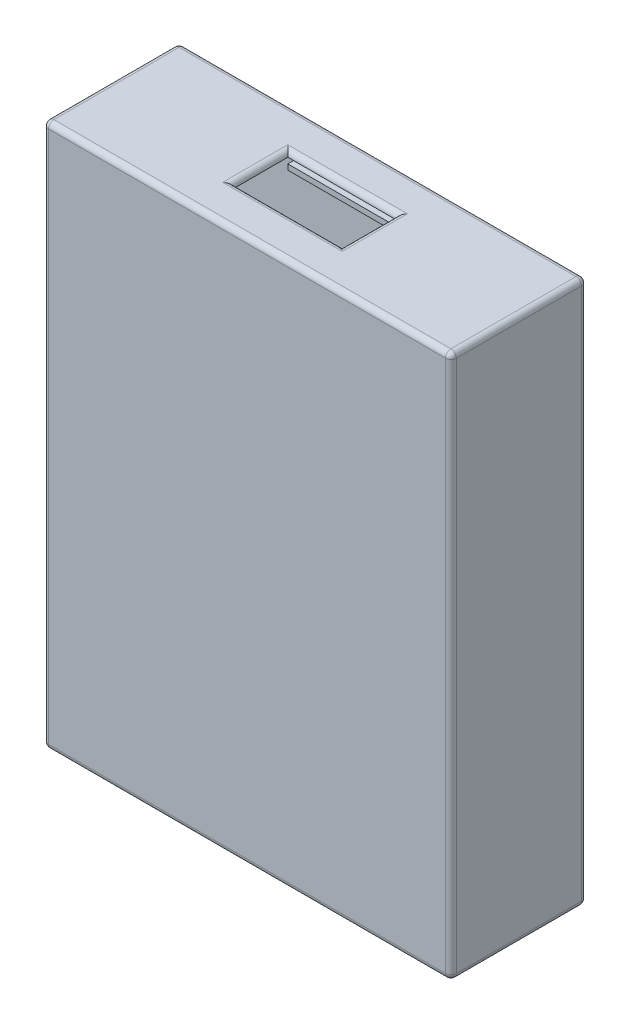
SolidWorks part; units mm, degrees
ref_plane "Front Plane" through (0, 0, 0) normal (0, 0, 1) x (1, 0, 0)
ref_plane "Top Plane" through (0, 0, 0) normal (0, 1, 0) x (1, 0, 0)
ref_plane "Right Plane" through (0, 0, 0) normal (1, 0, 0) x (0, 0, -1)
sketch "Sketch1" plane through (0, 0, 0) normal (0, 1, 0) x (1, 0, 0)
  line L1 (-75, 25) -> (75, 25)
  line L2 (-75, 25) -> (-75, -25)
  line L3 (-75, -25) -> (75, -25)
  line L4 (75, 25) -> (75, -25)
  line L5 (-75, 25) -> (75, -25) construction
  line L6 (-75, -25) -> (75, 25) construction
  point P0 (0, 0)
  dimension "D1" = 150
  dimension "D2" = 50
extrude "Boss-Extrude1" add sketch "Sketch1" along normal blind 30
sketch "Sketch2" plane through (0, 30, 0) normal (0, 1, 0) x (1, 0, 0)
  line L11 (-75, -25) -> (75, -25)
  line L12 (-75, -25) -> (-75, 25)
  line L13 (-75, 25) -> (75, 25)
  line L14 (-73, -23) -> (73, -23)
  line L15 (73, -23) -> (73, 23)
  line L16 (73, 23) -> (-73, 23)
  line L17 (-73, 23) -> (-73, -23)
  line L18 (-73, -23) -> (73, -23)
  line L19 (73, -23) -> (73, 23)
  line L20 (73, 23) -> (-73, 23)
  line L21 (-73, 23) -> (-73, -23)
  line L22 (75, -25) -> (75, 25)
  line L23 (-75, -25) -> (75, 25) construction
  line L24 (-75, 25) -> (75, -25) construction
  point P0 (0, 0)
  dimension "D1" = 2
extrude "Boss-Extrude2" add sketch "Sketch2" along normal blind 168
sketch "Sketch3" plane through (0, 198, 0) normal (0, 1, 0) x (1, 0, 0)
  line L1 (-75, -25) -> (75, -25)
  line L2 (-75, -25) -> (-75, 25)
  line L3 (-75, 25) -> (75, 25)
  line L4 (75, -25) -> (75, 25)
  line L5 (-75, -25) -> (75, 25) construction
  line L6 (-75, 25) -> (75, -25) construction
  point P0 (0, 0)
extrude "Boss-Extrude3" add sketch "Sketch3" along normal blind 2
sketch "Sketch4" plane through (0, 0, -25) normal (0, 0, -1) x (-1, 0, 0)
  line L0 (-73, 30) -> (0, 17.1281)
  line L1 (0, 17.1281) -> (73, 30)
  line L2 (-73, 30) -> (73, 30) construction
  line L3 (-73, 30) -> (73, 30)
  dimension "D1" = 10
  dimension "D2" = 10
extrude "Cut-Extrude1" cut sketch "Sketch4" against normal blind 65
sketch "Sketch6" plane through (0, 30, 0) normal (0, -1, 0) x (1, 0, 0)
  line L1 (-73, 25) -> (73, 25)
  line L2 (-73, 25) -> (-73, 23)
  line L3 (-73, 23) -> (73, 23)
  line L4 (73, 25) -> (73, 23)
extrude "Boss-Extrude13" add sketch "Sketch6" along normal blind 22
sketch "Sketch7" plane through (0, 30, 0) normal (0, -1, 0) x (1, 0, 0)
  line L1 (-73, -23) -> (73, -23)
  line L2 (-73, -23) -> (-73, -25)
  line L3 (-73, -25) -> (73, -25)
  line L4 (73, -23) -> (73, -25)
extrude "Boss-Extrude14" add sketch "Sketch7" along normal blind 22
sketch "Sketch8" plane through (0, 0, -25) normal (0, 0, -1) x (-1, 0, 0)
  circle A0 centre (0, 17.1281) radius 7.5
  dimension "D1" = 15
extrude "Cut-Extrude2" cut sketch "Sketch8" against normal blind 48
sketch "Sketch9" plane through (0, 200, 0) normal (0, 1, 0) x (1, 0, 0)
  line L1 (-20, -10) -> (20, -10)
  line L2 (-20, -10) -> (-20, 10)
  line L3 (-20, 10) -> (20, 10)
  line L4 (20, -10) -> (20, 10)
  line L5 (-20, -10) -> (20, 10) construction
  line L6 (-20, 10) -> (20, -10) construction
  point P0 (0, 0)
  dimension "D1" = 40
  dimension "D2" = 20
extrude "Cut-Extrude3" cut sketch "Sketch9" against normal blind 48
sketch "Sketch10" plane through (0, 0, -25) normal (0, 0, -1) x (-1, 0, 0)
  line L0 (75, 200) -> (-75, 0) construction
  line L1 (-75, 0) -> (-75, 200) construction
  line L2 (-75, 200) -> (75, 0) construction
  line L3 (0, 100) -> (0, 200) construction
  line L4 (-75, 200) -> (75, 200) construction
  line L5 (15.4707, 160) -> (15.4707, 118)
  line L6 (-13.5293, 160) -> (13.4707, 160)
  line L7 (-13.5293, 160) -> (-13.5293, 120)
  line L8 (-13.5293, 120) -> (13.4707, 120)
  line L9 (13.4707, 160) -> (13.4707, 120)
  line L10 (-15.5293, 118) -> (15.4707, 118)
  line L11 (-15.5293, 160) -> (-15.5293, 118)
  line L12 (-13.5293, 160) -> (-15.5293, 160)
  line L13 (13.4707, 160) -> (15.4707, 160)
  line L14 (-15.5293, 160) -> (-13.5293, 160)
  line L15 (13.4707, 160) -> (15.4707, 160)
  line L16 (-13.5293, 120) -> (13.4707, 120)
  circle A0 centre (0, 150) radius 4
  dimension "D1" = 27
  dimension "D2" = 40
  dimension "D3" = 10
  dimension "D4" = 2
extrude "Boss-Extrude15" add sketch "Sketch10" against normal blind 10 contours L13 L9 L8 L7 L12 L11 L10 L5 region at (-14.9487, 139, -25)
extrude "Cut-Extrude4" cut sketch "Sketch10<3>" against normal blind 5 contours A0 region at (0, 150, -25)
sketch "Sketch10<3>" plane through (0, 0, -25) normal (0, 0, -1) x (-1, 0, 0) same geometry as "Sketch10"
sketch "Sketch11" plane through (0, 0, -15) normal (0, 0, 1) x (1, 0, 0)
  line L0 (15.5293, 160) -> (15.5293, 118) construction
  line L1 (-15.4707, 160) -> (15.5293, 160)
  line L2 (-15.4707, 160) -> (-15.4707, 118)
  line L3 (-15.4707, 118) -> (15.5293, 118)
  line L4 (15.5293, 160) -> (15.5293, 118)
  line L5 (15.5293, 118) -> (-15.4707, 118) construction
extrude "Boss-Extrude16" add sketch "Sketch11" along normal blind 2
sketch "Sketch12" plane through (0, 160, 0) normal (0, 1, 0) x (1, 0, 0)
  line L0 (-15.4707, 13) -> (-15.4707, 23) construction
  line L2 (15.5293, 13) -> (-15.4707, 13) construction
  line L3 (-15.4707, 23) -> (-13.4707, 23) construction
  line L4 (15.5293, 13) -> (15.5293, 23) construction
  circle A0 centre (-14.4707, 14) radius 0.5
  circle A1 centre (-14.4707, 22) radius 0.5
  circle A2 centre (14.5293, 14) radius 0.5
  circle A3 centre (14.5293, 22) radius 0.5
  dimension "D1" = 1
  dimension "D3" = 1
  dimension "D5" = 1
  dimension "D2" = 1
  dimension "D4" = 1
  dimension "D6" = 1
extrude "Boss-Extrude17" add sketch "Sketch12" along normal blind 4
sketch "Sketch13" plane through (2.9291, 16.6117, 0) normal (0.1736, 0.9848, 0) x (0.9848, -0.1736, 0)
  line L1 (-10.4743, 23) -> (-25.4743, 23)
  line L2 (-10.4743, 23) -> (-10.4743, 19)
  line L3 (-10.4743, 19) -> (-25.4743, 19)
  line L4 (-25.4743, 23) -> (-25.4743, 19)
  dimension "D1" = 4
  dimension "D2" = 15
extrude "Cut-Extrude6" cut sketch "Sketch13" along direction (0, 1, 0) on the side against the normal blind 9
sketch "Sketch14" plane through (-7.3861, 0, 0) normal (-1, 0, 0) x (0, 0, 1)
  line L1 (-23, 9.4305) -> (-19, 9.4305)
  line L2 (-23, 9.4305) -> (-23, 15.8258)
  line L3 (-23, 15.8258) -> (-19, 15.8258)
  line L4 (-19, 9.4305) -> (-19, 15.8258)
extrude "Cut-Extrude7" cut sketch "Sketch14" against normal blind 6
sketch "Sketch15" plane through (0, 198, 0) normal (0, -1, 0) x (1, 0, 0)
  line L5 (20, 13) -> (-20, 13)
  line L6 (20, 13) -> (-20, 13)
  line L8 (-20, -13) -> (20, -13)
  line L9 (-20, -13) -> (20, -13)
  line L10 (-20, 13) -> (20, 13)
  line L11 (-20, 13) -> (-20, 15)
  line L12 (-20, 15) -> (20, 15)
  line L13 (20, 13) -> (20, 15)
  line L14 (-20, -13) -> (20, -13)
  line L15 (-20, -13) -> (-20, -15)
  line L16 (-20, -15) -> (20, -15)
  line L17 (20, -13) -> (20, -15)
  point P6 (-60.119, 27.344)
  dimension "D3" = 2
  dimension "D4" = 2
  dimension "D1" = 3
  dimension "D2" = 3
extrude "Boss-Extrude18" add sketch "Sketch15" along normal blind 2.1 contours L17 L9 L15 L16 | L11 L10 L13 L12 region at (0, 198, -14)
sketch "Sketch16" plane through (0, 195.9, 0) normal (0, -1, 0) x (1, 0, 0)
  line L1 (-20, 15) -> (20, 15)
  line L2 (-20, 15) -> (-20, 10)
  line L3 (-20, 10) -> (20, 10)
  line L4 (20, 15) -> (20, 10)
  line L5 (-20, -15) -> (20, -15)
  line L6 (-20, -15) -> (-20, -10)
  line L7 (-20, -10) -> (20, -10)
  line L8 (20, -15) -> (20, -10)
extrude "Boss-Extrude19" add sketch "Sketch16" along normal blind 2
sketch "Sketch17" plane through (20, 0, 0) normal (1, 0, 0) x (0, 0, -1)
  line L0 (-15, 198) -> (-15, 193.9)
  line L1 (-15, 193.9) -> (-10, 193.9)
  line L2 (-10, 193.9) -> (-10, 195.9)
  line L3 (-10, 193.9) -> (-10, 195.9) construction
  line L4 (-10, 195.9) -> (-13, 195.9)
  line L5 (-13, 195.9) -> (-13, 198)
  line L6 (-13, 198) -> (-15, 198) construction
  line L7 (-13, 195.9) -> (-13, 198) construction
  line L8 (-13, 198) -> (-15, 198)
  line L9 (13, 198) -> (15, 198)
  line L10 (15, 198) -> (15, 193.9)
  line L11 (15, 193.9) -> (10, 193.9)
  line L12 (10, 193.9) -> (10, 195.9)
  line L13 (10, 195.9) -> (13, 195.9)
  line L14 (13, 195.9) -> (13, 198)
extrude "Boss-Extrude20" add sketch "Sketch17" along normal blind 40
sketch "Sketch18" plane through (60, 0, 0) normal (1, 0, 0) x (0, 0, -1)
  line L1 (-15, 193.9) -> (15, 193.9)
  line L2 (-15, 193.9) -> (-15, 198)
  line L3 (-15, 198) -> (15, 198)
  line L4 (15, 193.9) -> (15, 198)
extrude "Boss-Extrude21" add sketch "Sketch18" along normal blind 2
sketch "Sketch20" plane through (0, 0, -23) normal (0, 0, 1) x (1, 0, 0)
  line L0 (0, 9.6281) -> (0, 41.091) construction
  line L1 (-5.7, 39.8781) -> (18.3, 39.8781)
  line L2 (-5.7, 37.8781) -> (16.3, 37.8781)
  line L3 (-5.7, 37.8781) -> (-5.7, 26.3781)
  line L4 (-5.7, 26.3781) -> (16.3, 26.3781)
  line L5 (16.3, 37.8781) -> (16.3, 26.3781)
  line L6 (18.3, 39.8781) -> (18.3, 24.3781)
  line L7 (-5.7, 24.3781) -> (18.3, 24.3781)
  line L8 (-5.7, 39.8781) -> (-5.7, 37.8781)
  line L9 (3.3, 26.3781) -> (3.3, 24.3781)
  circle A0 centre (0, 17.1281) radius 7.5 construction
  point P10 (0, 32.1281)
  point P11 (0, 17.1281)
  dimension "D1" = 16.3
  dimension "D2" = 22
  dimension "D3" = 11.5
  dimension "D4" = 7.5
  dimension "D5" = 15
  dimension "D6" = 5.75
  dimension "D8" = 15
  dimension "D7" = 2
extrude "Boss-Extrude22" add sketch "Sketch20" along normal blind 31 contours L0 L2 L5 L4 L9 L7 L6 L1 | L2 L0 L1 L8 region at (3.5398, 25.3781, -23) region at (-2.85, 38.8781, -23)
sketch "Sketch21" plane through (0, 0, 8) normal (0, 0, 1) x (1, 0, 0)
  line L0 (-5.7, 39.8781) -> (-5.7, 37.8781) construction
  line L1 (18.3, 39.8781) -> (-5.7, 39.8781)
  line L2 (18.3, 39.8781) -> (18.3, 24.3781)
  line L3 (18.3, 24.3781) -> (-5.7, 24.3781)
  line L4 (-5.7, 39.8781) -> (-5.7, 24.3781)
  line L5 (3.3, 24.3781) -> (18.3, 24.3781) construction
  dimension "D1" = 0
  dimension "D2" = 0
extrude "Boss-Extrude23" add sketch "Sketch21" along normal blind 2
fillet "Fillet1" radius 2 16 edges at (0, 200, -25) (-20, 200, 0) (0, 200, 10) (20, 200, 0) (0, 200, -10) (0, 0, -25) (0, 200, 25) (0, 0, 25) (75, 100, 25) (75, 200, 0) (75, 100, -25) (75, 0, 0) (-75, 100, -25) (-75, 200, 0) (-75, 100, 25) (-75, 0, 0)
